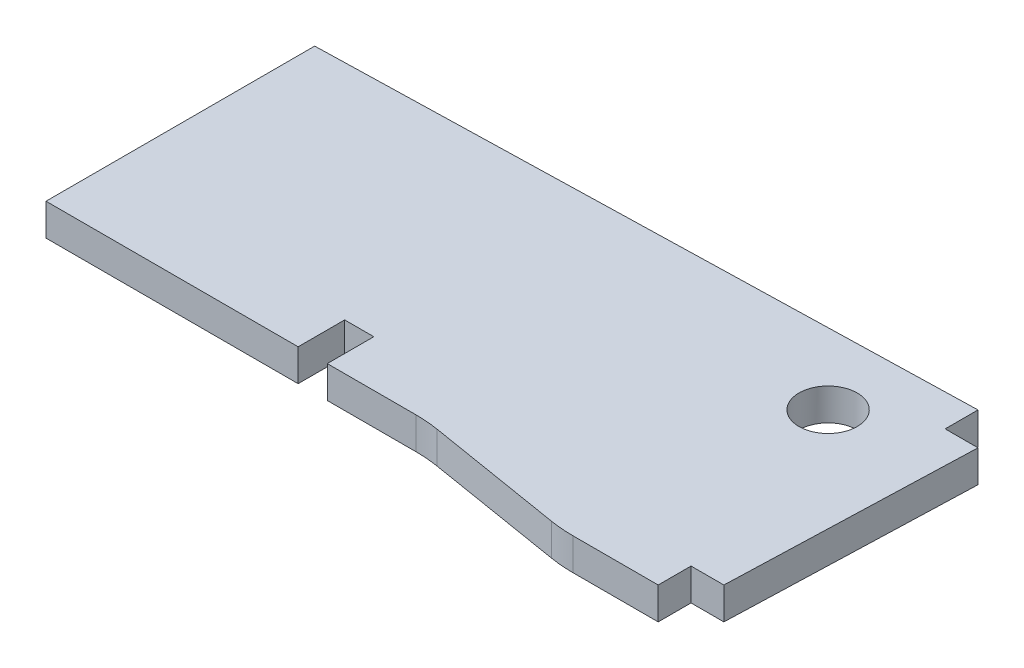
SolidWorks part; units mm, degrees
material "Pine"
ref_plane "Front Plane" through (0, 0, 0) normal (0, 0, 1) x (1, 0, 0)
ref_plane "Top Plane" through (0, 0, 0) normal (0, 1, 0) x (1, 0, 0)
ref_plane "Right Plane" through (0, 0, 0) normal (1, 0, 0) x (0, 0, -1)
sketch "Sketch1" plane through (0, 0, 0) normal (0, 1, 0) x (1, 0, 0)
  line L0 (0, 0) -> (0, 23.9014)
  line L1 (0, 23.9014) -> (57.531, 25.3746)
  line L2 (57.531, 25.3746) -> (57.531, 22.4536)
  line L3 (57.531, 22.4536) -> (60.452, 22.4536)
  line L4 (60.452, 22.4536) -> (59.7154, 0.5842)
  line L5 (59.7154, 0.5842) -> (56.7944, 0.5842)
  line L6 (56.7944, 0.5842) -> (56.7944, -2.3368)
  line L7 (0, 0) -> (33.9344, 0)
  line L8 (56.7944, -2.3368) -> (48.1584, -2.3368)
  line L9 (33.9344, 0) -> (48.1584, -2.3368)
  point P3 (0, 0)
  dimension "D1" = 60.452
  dimension "D2" = 2.921
  dimension "D3" = 22.86
  dimension "D4" = 59.7154
  dimension "D5" = 8.636
  dimension "D6" = 23.9014
  dimension "D7" = 21.8694
  dimension "D9" = 1.4732
extrude "Boss-Extrude1" add sketch "Sketch1" along normal blind 2.8448
fillet "Fillet1" radius 12.7 2 edges at (48.1584, 1.4224, 2.3368) (33.9344, 1.4224, 0)
sketch "Sketch2" plane through (0, 2.8448, 0) normal (0, 1, 0) x (1, 0, 0)
  line L0 (0, 0) -> (32.8981, 0) construction
  line L1 (22.4282, 0) -> (25.019, 0)
  line L2 (22.4282, 0) -> (22.4282, 4.1402)
  line L3 (22.4282, 4.1402) -> (25.019, 4.1402)
  line L4 (25.019, 0) -> (25.019, 4.1402)
  line L5 (0, 23.9014) -> (0, 0) construction
  dimension "D1" = 4.1402
  dimension "D2" = 2.5908
  dimension "D3" = 22.4282
extrude "Cut-Extrude1" cut sketch "Sketch2" against normal up to next
sketch "Sketch3" plane through (0, 2.8448, 0) normal (0, 1, 0) x (1, 0, 0)
  line L0 (48.26, 18.7198) -> (48.26, 31.4977) construction
  line L1 (0, 23.9014) -> (0, 0) construction
  line L2 (50.8508, 16.129) -> (40.3347, 16.129) construction
  line L3 (49.1947, -2.3368) -> (56.7944, -2.3368) construction
  circle A0 centre (50.8508, 18.7198) radius 2.5908
  dimension "D1" = 5.1816
  dimension "D2" = 48.26
  dimension "D3" = 18.4658
extrude "Cut-Extrude2" cut sketch "Sketch3" against normal up to next
